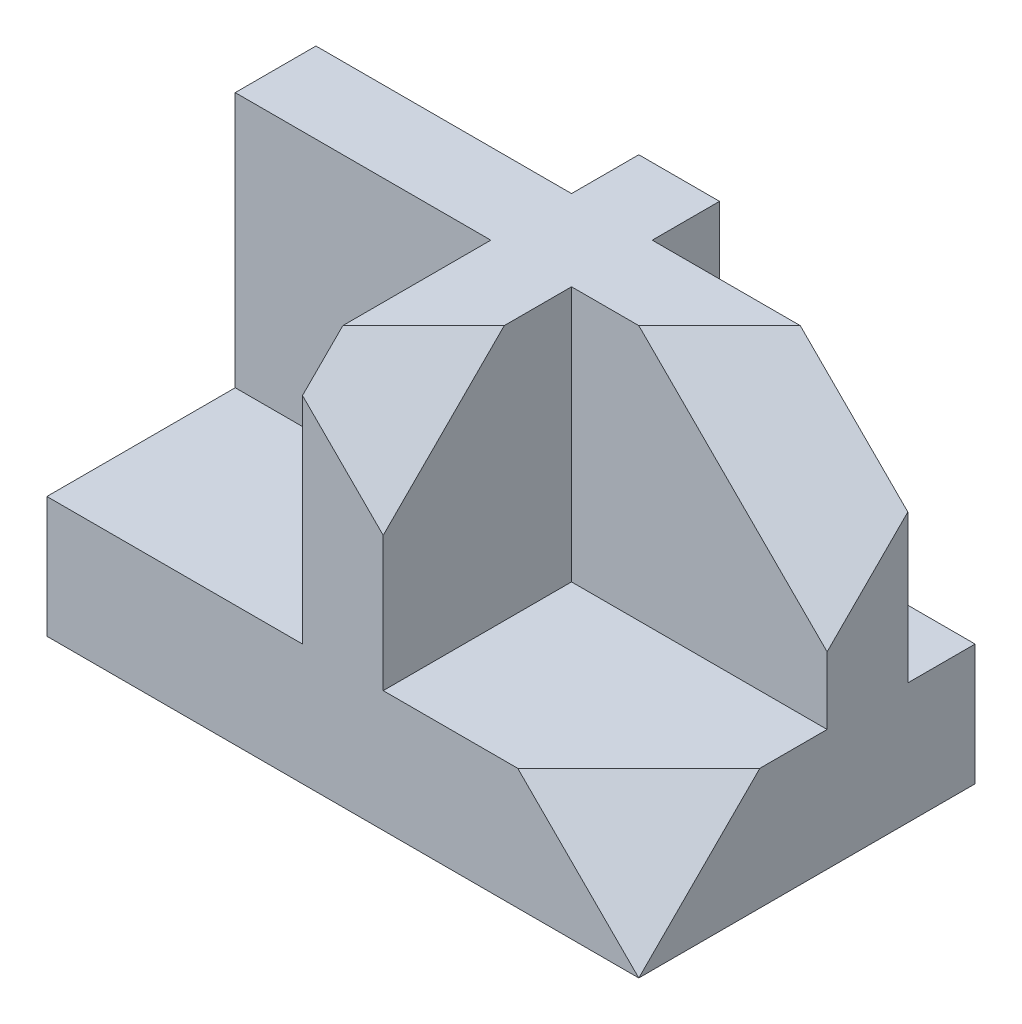
SolidWorks part; units mm, degrees
note: The reader was unsure of these and kept them because the rebuilt part matched: shared geometry of "Sketch1<3>".
ref_plane "Front Plane" through (0, 0, 0) normal (0, 0, 1) x (1, 0, 0)
ref_plane "Top Plane" through (0, 0, 0) normal (0, 1, 0) x (1, 0, 0)
ref_plane "Right Plane" through (0, 0, 0) normal (1, 0, 0) x (0, 0, -1)
sketch "Sketch1" plane through (0, 0, 0) normal (0, 1, 0) x (1, 0, 0)
  line L1 (-44, 25) -> (44, 25)
  line L2 (-44, 25) -> (-44, -25)
  line L3 (-44, -25) -> (44, -25)
  line L4 (44, 25) -> (44, -25)
  line L5 (-44, 25) -> (44, -25) construction
  line L6 (-44, -25) -> (44, 25) construction
  line L7 (-6, 25) -> (6, 25)
  line L8 (-6, 25) -> (-6, -25)
  line L9 (-6, -25) -> (6, -25)
  line L10 (6, 25) -> (6, -25)
  line L11 (-44, 15) -> (44, 15)
  line L12 (-44, 15) -> (-44, 3)
  line L13 (-44, 3) -> (44, 3)
  line L14 (44, 15) -> (44, 3)
  point P0 (0, 0)
  dimension "D1" = 50
  dimension "D2" = 88
  dimension "D3" = 12
  dimension "D4" = 12
  dimension "D5" = 28
  dimension "D6" = 38
extrude "Boss-Extrude1" add sketch "Sketch1" against normal blind 18 contours L10 L11 L4 L1 | L10 L13 L4 L11 | L8 L13 L10 L11 | L13 L10 L3 L4 | L13 L8 L3 L10 | L13 L2 L3 L8 | L2 L13 L8 L11 | L2 L11 L8 L1 | L8 L11 L10 L1
extrude "Boss-Extrude2" add sketch "Sketch1<3>" along normal blind 38 contours L2 L13 L8 L11 | L8 L13 L10 L11 | L10 L13 L4 L11 | L13 L8 L3 L10 | L8 L11 L10 L1
sketch "Sketch1<3>" plane through (0, 0, 0) normal (0, 1, 0) x (1, 0, 0) same geometry as "Sketch1"
sketch "Sketch2" plane through (0, 0, -25) normal (0, 0, -1) x (-1, 0, 0)
sketch "Sketch4" plane through (0, 0, 25) normal (0, 0, 1) x (1, 0, 0)
  line L0 (44, -18) -> (-9.9842, 35.9842) construction
  line L1 (-44, -18) -> (44, -18) construction
  dimension "D1" = 45
sketch "Sketch5" plane through (44, 0, 0) normal (1, 0, 0) x (0, 0, -1)
  line L0 (-25, -18) -> (18.2863, 25.2863) construction
  line L1 (-25, -18) -> (-25, 35.9842) construction
  line L2 (25, -18) -> (-25, -18) construction
  dimension "D1" = 45
ref_plane "Plane2" through (17, 17, 17) normal (0.5774, 0.5774, 0.5774) x (0.8165, -0.4082, -0.4082)
other "SurfaceCut5" flip cut yes
